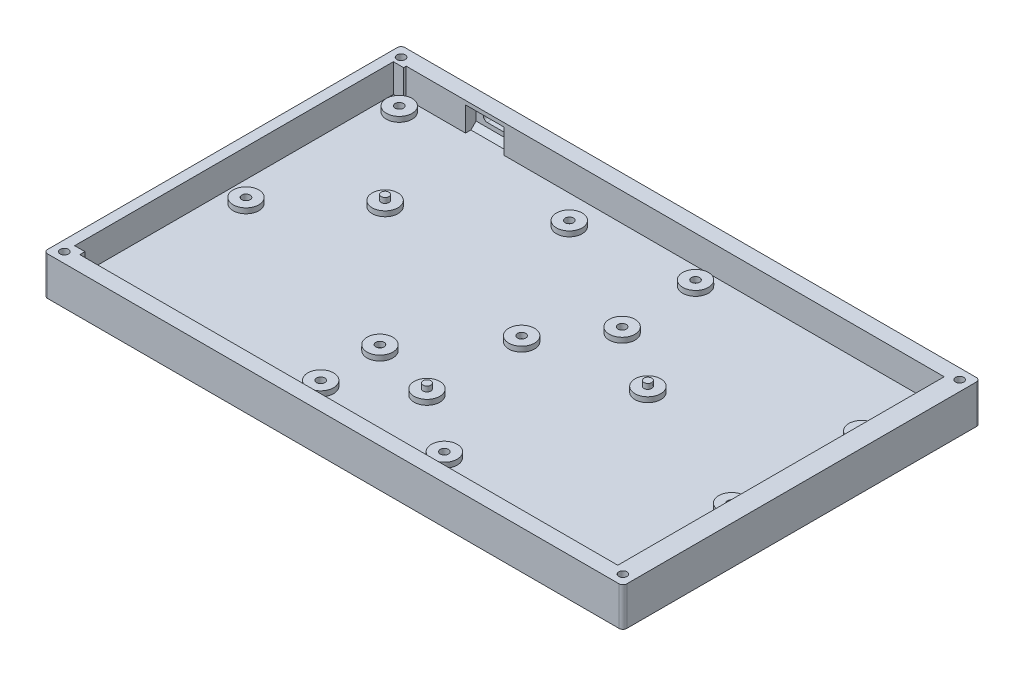
SolidWorks part; units mm, degrees
ref_plane "Front Plane" through (0, 0, 0) normal (0, 0, 1) x (1, 0, 0)
ref_plane "Top Plane" through (0, 0, 0) normal (0, 1, 0) x (1, 0, 0)
ref_plane "Right Plane" through (0, 0, 0) normal (1, 0, 0) x (0, 0, -1)
sketch "Sketch1" plane through (0, 0, 0) normal (0, 1, 0) x (1, 0, 0)
  line L1 (44.992, 213.0031) -> (269.802, 213.0031)
  line L2 (44.992, 213.0031) -> (44.992, 351.7031)
  line L3 (44.992, 351.7031) -> (269.802, 351.7031)
  line L4 (269.802, 213.0031) -> (269.802, 351.7031)
  dimension "D1" = 138.7
  dimension "D2" = 224.81
extrude "bottom_plate" add sketch "Sketch1" along normal blind 4
sketch "Sketch2" plane through (0, 4, 0) normal (0, 1, 0) x (1, 0, 0)
  line L9 (44.992, 213.0031) -> (52.992, 213.0031)
  line L10 (44.992, 213.0031) -> (44.992, 221.0031)
  line L11 (44.992, 221.0031) -> (52.992, 221.0031)
  line L12 (52.992, 213.0031) -> (52.992, 221.0031)
  line L13 (269.802, 213.0031) -> (262.802, 213.0031)
  line L14 (269.802, 213.0031) -> (269.802, 220.0031)
  line L15 (269.802, 220.0031) -> (262.802, 220.0031)
  line L16 (262.802, 213.0031) -> (262.802, 220.0031)
  line L17 (269.802, 351.7031) -> (262.802, 351.7031)
  line L18 (269.802, 351.7031) -> (269.802, 344.7031)
  line L19 (269.802, 344.7031) -> (262.802, 344.7031)
  line L20 (262.802, 351.7031) -> (262.802, 344.7031)
  line L21 (44.992, 351.7031) -> (52.992, 351.7031)
  line L22 (44.992, 351.7031) -> (44.992, 344.7031)
  line L23 (44.992, 344.7031) -> (52.992, 344.7031)
  line L24 (52.992, 351.7031) -> (52.992, 344.7031)
  dimension "D1" = 8
  dimension "D2" = 7
extrude "side_walls" add sketch "Sketch2" along normal blind 11
sketch "Sketch11" plane through (0, 4, 0) normal (0, 1, 0) x (1, 0, 0)
  line L0 (52.992, 221.0031) -> (44.992, 221.0031) construction
  line L1 (44.992, 344.7031) -> (48.992, 344.7031)
  line L2 (44.992, 344.7031) -> (44.992, 221.0031)
  line L3 (44.992, 221.0031) -> (48.992, 221.0031)
  line L4 (48.992, 344.7031) -> (48.992, 221.0031)
  line L5 (262.802, 220.0031) -> (262.802, 213.0031) construction
  line L6 (52.992, 213.0031) -> (262.802, 213.0031)
  line L7 (52.992, 213.0031) -> (52.992, 219.0031)
  line L8 (52.992, 219.0031) -> (261.802, 219.0031)
  line L9 (262.802, 213.0031) -> (262.802, 219.0031)
  line L11 (269.802, 219.0031) -> (262.802, 219.0031)
  line L12 (269.802, 219.0031) -> (269.802, 345.7031)
  line L13 (269.802, 345.7031) -> (262.802, 345.7031)
  line L14 (261.802, 219.0031) -> (261.802, 345.7031)
  line L15 (52.992, 344.7031) -> (52.992, 351.7031) construction
  line L16 (262.802, 351.7031) -> (52.992, 351.7031)
  line L17 (262.802, 351.7031) -> (262.802, 345.7031)
  line L18 (261.802, 345.7031) -> (90.992, 345.7031)
  line L19 (52.992, 351.7031) -> (52.992, 345.7031)
  line L20 (75.992, 345.7031) -> (52.992, 345.7031)
  line L22 (90.992, 345.7031) -> (90.992, 349.8031)
  line L23 (90.992, 349.8031) -> (75.992, 349.8031)
  line L24 (75.992, 345.7031) -> (75.992, 349.8031)
  line L25 (269.802, 220.0031) -> (269.802, 344.7031) construction
  dimension "D1" = 8
  dimension "D2" = 6
  dimension "D3" = 6
  dimension "D4" = 4
  dimension "D5" = 4.1
  dimension "D6" = 31
  dimension "D7" = 15
extrude "usb_cutout" add sketch "Sketch11" along normal up to surface (11 mm away) up to face at (266.302, 15, -216.5031)
hole_wizard "CSK for M3 SFHCS1" positions "Sketch5" profile "Sketch6" countersink size "M3" standard "ANSI Metric" end condition through all
sketch "Sketch5" plane through (0, 0, 0) normal (0, -1, 0) x (-1, 0, 0)
  point P42 (-48.992, 217.0037)
  point P45 (-265.7999, 217.0037)
  point P48 (-265.7999, 347.7031)
  point P51 (-48.992, 347.7031)
sketch "Sketch6" plane through (48.992, 0, -217.0037) normal (1, 0, 0) x (0, 0, -1)
  line L0 (0, 0) -> (0, 15)
  line L1 (0, 15) -> (1.6, 15)
  line L2 (1.6, 15) -> (1.6, 1.76)
  line L3 (1.6, 1.76) -> (3.36, 0)
  line L5 (3.36, 0) -> (0, 0)
  line L6 (-1.6, 1.76) -> (-3.36, 0) construction
  line L11 (0, -6.35) -> (0, 107.95) construction
  dimension "Thru Hole Dia." = 3.2
  dimension "Thru Hole Depth" = 15
  dimension "Near C'Sink Dia." = 6.72
  dimension "Near C'Sink Angle" = 90
fillet "Fillet1" radius 1.5 4 edges at (44.992, 7.5, -351.7031) (44.992, 7.5, -213.0031) (269.802, 7.5, -351.7031) (269.802, 7.5, -213.0031)
sketch "Sketch14" plane through (0, 0, -349.8031) normal (0, 0, 1) x (1, 0, 0)
  line L0 (44.992, 15) -> (44.992, 0) construction
  line L9 (80.3002, 7.7) -> (86.4707, 7.7)
  line L10 (78.8002, 9.2) -> (78.8002, 9.5905)
  line L11 (80.3002, 11.0905) -> (86.4707, 11.0905)
  line L12 (87.9707, 9.2) -> (87.9707, 9.5905)
  line L13 (268.302, 0) -> (46.492, 0) construction
  arc A4 (78.8002, 9.5905) -> (80.3002, 11.0905) centre (80.3002, 9.5905) cw
  arc A5 (80.3002, 7.7) -> (78.8002, 9.2) centre (80.3002, 9.2) cw
  arc A6 (86.4707, 7.7) -> (87.9707, 9.2) centre (86.4707, 9.2) ccw
  arc A7 (86.4707, 11.0905) -> (87.9707, 9.5905) centre (86.4707, 9.5905) cw
  dimension "D1" = 9.1705
  dimension "D5" = 1.5
  dimension "D2" = 3.3905
  dimension "D3" = 33.8083
  dimension "D4" = 7.7
extrude "usb-c port" cut sketch "Sketch14" against normal blind 10
sketch "Sketch18" plane through (0, 15, 0) normal (0, 1, 0) x (1, 0, 0)
  line L1 (75.992, 345.7031) -> (90.992, 345.7031)
  line L2 (75.992, 345.7031) -> (75.992, 349.8031)
  line L3 (75.992, 349.8031) -> (90.992, 349.8031)
  line L4 (90.992, 345.7031) -> (90.992, 349.8031)
extrude "Boss-Extrude1" add sketch "Sketch18" against normal blind 1.5
chamfer "Chamfer1" distance 2 angle 45 2 edges at (83.492, 4, -349.8031) (83.492, 13.5, -349.8031)
sketch "Sketch16" plane through (0, 4, 0) normal (0, 1, 0) x (1, 0, 0)
  circle A0 centre (55.992, 340.0037) radius 5
  circle A1 centre (56.992, 279.5037) radius 5
  circle A2 centre (132.492, 256.0037) radius 5
  circle A4 centre (253.992, 271.0037) radius 5
  circle A5 centre (254.992, 320.5037) radius 5
  circle A6 centre (156.992, 286.5037) radius 5
  circle A7 centre (171.992, 339.0037) radius 5
  circle A8 centre (127.492, 334.5037) radius 5
  circle A9 centre (173.492, 309.0037) radius 5
  circle A10 centre (198.492, 294.0037) radius 5
  circle A11 centre (180.992, 232.5037) radius 5
  circle A12 centre (84.992, 305.5037) radius 5
  circle A15 centre (156.492, 250.2537) radius 5
  circle A29 centre (132.992, 232.5037) radius 5
  point P2 (55.8081, 339.9025)
  point P5 (55.992, 340.0037)
  point P8 (84.992, 305.5037)
  point P9 (56.992, 279.5037)
  point P10 (132.492, 256.0037)
  point P11 (156.492, 250.2537)
  point P14 (156.992, 286.5037)
  point P17 (173.492, 309.0037)
  point P20 (171.992, 339.0037)
  point P23 (254.992, 320.5037)
  point P26 (253.992, 271.0037)
  point P29 (198.492, 294.0037)
  point P32 (181.5256, 231.8873)
  point P35 (180.992, 232.5037)
  point P38 (132.992, 232.5037)
  dimension "D1" = 10
extrude "pcb_support" add sketch "Sketch16" along normal blind 2 contours A0 | A12 | A1 | A7 | A8 | A6 | A11 | A10 | A5 | A4 | A9 | A2 | A15 | A29 region at (55.992, 4, -340.0037) region at (56.992, 4, -279.5037) region at (253.992, 4, -271.0037) region at (254.992, 4, -320.5037) region at (156.992, 4, -286.5037) region at (171.992, 4, -339.0037) region at (127.492, 4, -334.5037) region at (198.492, 4, -294.0037) region at (180.992, 4, -232.5037) region at (84.992, 4, -305.5037)
sketch "Sketch17" plane through (0, 6, 0) normal (0, 1, 0) x (1, 0, 0)
  circle A0 centre (84.992, 305.5037) radius 1.5
  circle A1 centre (198.492, 294.0037) radius 1.5
  circle A2 centre (84.992, 305.5037) radius 5 construction
  circle A3 centre (156.492, 250.2537) radius 1.5
  dimension "D1" = 3
  dimension "D2" = 3
  dimension "D3" = 3
extrude "alignment_posts" add sketch "Sketch17" along normal blind 2
sketch "Sketch20" plane through (0, 6, 0) normal (0, 1, 0) x (1, 0, 0)
  circle A0 centre (55.992, 340.0037) radius 1.6
  circle A1 centre (127.492, 334.5037) radius 1.6
  circle A2 centre (56.992, 279.5037) radius 1.6
  circle A3 centre (132.492, 256.0037) radius 1.6
  circle A4 centre (132.992, 232.5037) radius 1.6
  circle A5 centre (180.992, 232.5037) radius 1.6
  circle A6 centre (156.992, 286.5037) radius 1.6
  circle A7 centre (253.992, 271.0037) radius 1.6
  circle A8 centre (173.492, 309.0037) radius 1.6
  circle A9 centre (171.992, 339.0037) radius 1.6
  circle A10 centre (254.992, 320.5037) radius 1.6
  dimension "D1" = 3.2
extrude "pcb screw clearance" cut sketch "Sketch20" against normal blind 2.15
sketch "Sketch21" plane through (0, 3.85, 0) normal (0, 1, 0) x (1, 0, 0)
  line L1 (53.242, 342.7537) -> (58.742, 342.7537)
  line L2 (53.242, 342.7537) -> (53.242, 337.2537)
  line L3 (53.242, 337.2537) -> (58.742, 337.2537)
  line L4 (58.742, 342.7537) -> (58.742, 337.2537)
  line L5 (53.242, 342.7537) -> (58.742, 337.2537) construction
  line L6 (53.242, 337.2537) -> (58.742, 342.7537) construction
  line L7 (124.742, 337.2537) -> (130.242, 337.2537)
  line L8 (124.742, 337.2537) -> (124.742, 331.7537)
  line L9 (124.742, 331.7537) -> (130.242, 331.7537)
  line L10 (130.242, 337.2537) -> (130.242, 331.7537)
  line L11 (124.742, 337.2537) -> (130.242, 331.7537) construction
  line L12 (124.742, 331.7537) -> (130.242, 337.2537) construction
  line L13 (54.242, 282.2537) -> (59.742, 282.2537)
  line L14 (54.242, 282.2537) -> (54.242, 276.7537)
  line L15 (54.242, 276.7537) -> (59.742, 276.7537)
  line L16 (59.742, 282.2537) -> (59.742, 276.7537)
  line L17 (54.242, 282.2537) -> (59.742, 276.7537) construction
  line L18 (54.242, 276.7537) -> (59.742, 282.2537) construction
  line L19 (129.742, 258.7537) -> (135.242, 258.7537)
  line L20 (129.742, 258.7537) -> (129.742, 253.2537)
  line L21 (129.742, 253.2537) -> (135.242, 253.2537)
  line L22 (135.242, 258.7537) -> (135.242, 253.2537)
  line L23 (129.742, 258.7537) -> (135.242, 253.2537) construction
  line L24 (129.742, 253.2537) -> (135.242, 258.7537) construction
  line L25 (135.742, 235.2537) -> (130.242, 235.2537)
  line L26 (135.742, 235.2537) -> (135.742, 229.7537)
  line L27 (135.742, 229.7537) -> (130.242, 229.7537)
  line L28 (130.242, 235.2537) -> (130.242, 229.7537)
  line L29 (135.742, 235.2537) -> (130.242, 229.7537) construction
  line L30 (135.742, 229.7537) -> (130.242, 235.2537) construction
  line L31 (178.242, 229.7537) -> (183.742, 229.7537)
  line L32 (178.242, 229.7537) -> (178.242, 235.2537)
  line L33 (178.242, 235.2537) -> (183.742, 235.2537)
  line L34 (183.742, 229.7537) -> (183.742, 235.2537)
  line L35 (178.242, 229.7537) -> (183.742, 235.2537) construction
  line L36 (178.242, 235.2537) -> (183.742, 229.7537) construction
  line L37 (256.742, 273.7537) -> (251.242, 273.7537)
  line L38 (256.742, 273.7537) -> (256.742, 268.2537)
  line L39 (256.742, 268.2537) -> (251.242, 268.2537)
  line L40 (251.242, 273.7537) -> (251.242, 268.2537)
  line L41 (256.742, 273.7537) -> (251.242, 268.2537) construction
  line L42 (256.742, 268.2537) -> (251.242, 273.7537) construction
  line L43 (170.742, 306.2537) -> (176.242, 306.2537)
  line L44 (170.742, 306.2537) -> (170.742, 311.7537)
  line L45 (170.742, 311.7537) -> (176.242, 311.7537)
  line L46 (176.242, 306.2537) -> (176.242, 311.7537)
  line L47 (170.742, 306.2537) -> (176.242, 311.7537) construction
  line L48 (170.742, 311.7537) -> (176.242, 306.2537) construction
  line L49 (169.242, 336.2537) -> (174.742, 336.2537)
  line L50 (169.242, 336.2537) -> (169.242, 341.7537)
  line L51 (169.242, 341.7537) -> (174.742, 341.7537)
  line L52 (174.742, 336.2537) -> (174.742, 341.7537)
  line L53 (169.242, 336.2537) -> (174.742, 341.7537) construction
  line L54 (169.242, 341.7537) -> (174.742, 336.2537) construction
  line L55 (252.242, 317.7537) -> (257.742, 317.7537)
  line L56 (252.242, 317.7537) -> (252.242, 323.2537)
  line L57 (252.242, 323.2537) -> (257.742, 323.2537)
  line L58 (257.742, 317.7537) -> (257.742, 323.2537)
  line L59 (252.242, 317.7537) -> (257.742, 323.2537) construction
  line L60 (252.242, 323.2537) -> (257.742, 317.7537) construction
  point P0 (55.992, 340.0037)
  point P6 (127.492, 334.5037)
  point P12 (56.992, 279.5037)
  point P18 (132.492, 256.0037)
  point P24 (132.992, 232.5037)
  point P30 (180.992, 232.5037)
  point P36 (253.992, 271.0037)
  point P42 (173.492, 309.0037)
  point P48 (171.992, 339.0037)
  point P54 (254.992, 320.5037)
  dimension "D1" = 5.5
extrude "Cut-Extrude2" cut sketch "Sketch21" against normal blind 1.8
